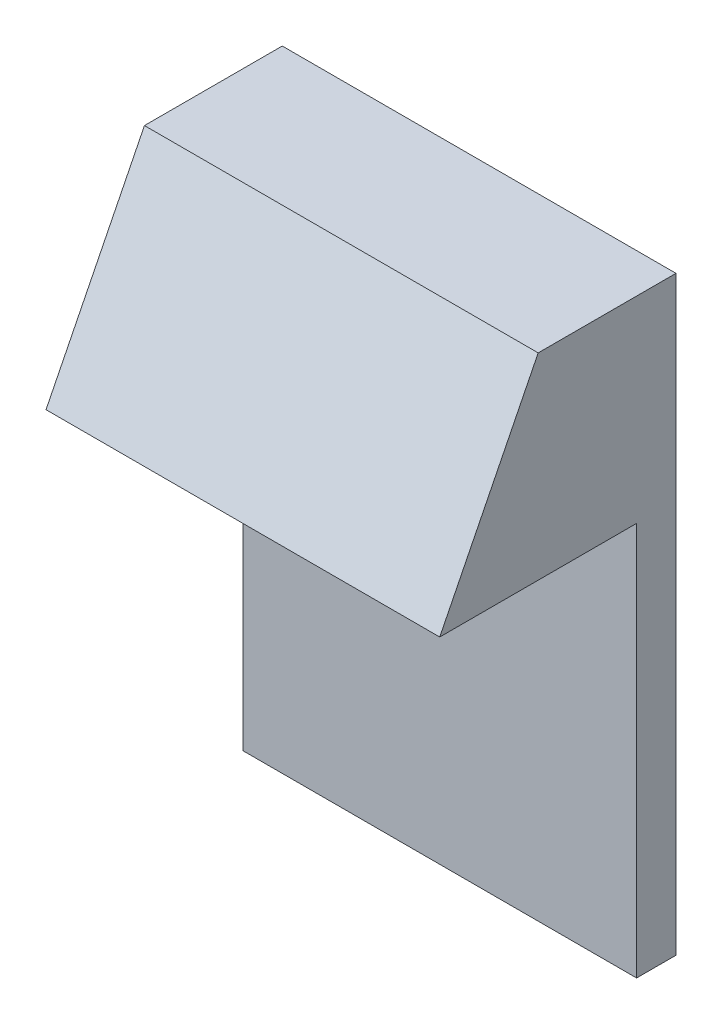
SolidWorks part; units mm, degrees
ref_plane "Front" through (0, 0, 0) normal (0, 0, 1) x (1, 0, 0)
ref_plane "Top" through (0, 0, 0) normal (0, 1, 0) x (1, 0, 0)
ref_plane "Right" through (0, 0, 0) normal (1, 0, 0) x (0, 0, -1)
sketch "Sketch1" plane through (0, 0, 0) normal (0, 0, 1) x (1, 0, 0)
  line L1 (0, 0) -> (20, 0)
  line L2 (0, 0) -> (0, 30)
  line L3 (0, 30) -> (20, 30)
  line L4 (20, 0) -> (20, 30)
  dimension "D1" = 30
  dimension "D2" = 20
extrude "Boss-Extrude1" add sketch "Sketch1" along normal blind 2
sketch "Sketch3" plane through (20, 0, 0) normal (1, 0, 0) x (0, 0, -1)
  line L0 (-2, 20) -> (-12, 20)
  line L1 (-2, 0) -> (-2, 30) construction
  line L2 (-12, 20) -> (-7, 30)
  line L3 (-7, 30) -> (-2, 30)
  line L4 (-2, 30) -> (0, 30) construction
  line L5 (-2, 30) -> (-2, 20)
  dimension "D1" = 10
  dimension "D2" = 10
  dimension "D3" = 5
extrude "Boss-Extrude2" add sketch "Sketch3" against normal blind 20
